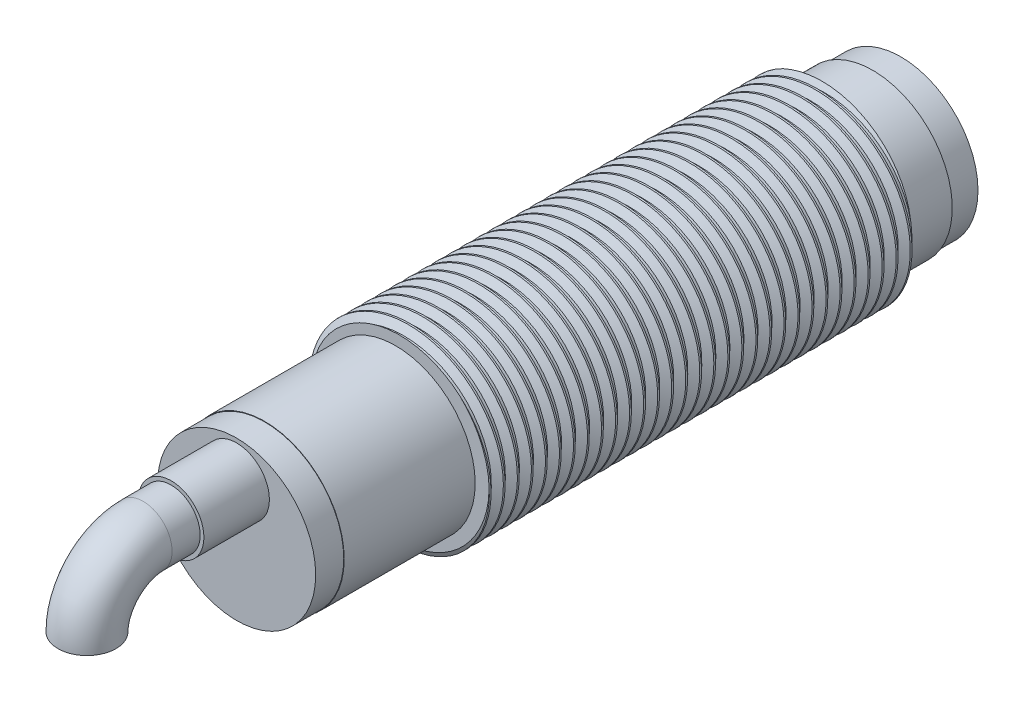
SolidWorks part; units mm, degrees
ref_plane "Front Plane" through (0, 0, 0) normal (0, 0, 1) x (1, 0, 0)
ref_plane "Top Plane" through (0, 0, 0) normal (0, 1, 0) x (1, 0, 0)
ref_plane "Right Plane" through (0, 0, 0) normal (1, 0, 0) x (0, 0, -1)
sketch "Sketch1" plane through (0, 0, 0) normal (0, 0, 1) x (1, 0, 0)
  circle A0 centre (0, 0) radius 8.25
  dimension "D1" = 16.5
extrude "Boss-Extrude1" add sketch "Sketch1" along normal blind 3
sketch "Sketch2" plane through (0, 0, 3) normal (0, 0, 1) x (1, 0, 0)
  circle A1 centre (0, 0) radius 10
  dimension "D1" = 20
extrude "Boss-Extrude2" add sketch "Sketch2" along normal blind 65
sketch "Sketch3" plane through (0, 0, 68) normal (0, 0, 1) x (1, 0, 0)
  circle A0 centre (0, 0) radius 8.45
  dimension "16.9" = 16.9
extrude "Boss-Extrude3" add sketch "Sketch3" along normal blind 3
thread "Thread1" pitch 1.5 profile "Thread Profile1" start angle 2, offset 3, length 48, pitch 1.5, diameter 20
ref_plane "Plane1" through (9.9939, 0.349, 6) normal (0.0349, -0.9994, 0) x (0.9994, 0.0349, 0)
sketch "Thread Profile1" plane through (9.9939, 0.349, 6) normal (0.0349, -0.9994, 0) x (0.9994, 0.0349, 0)
  line L0 (0, 0) -> (0, 1.5) construction
  line L11 (0, 0) -> (0, 1.3125)
  line L12 (0, 1.3125) -> (-0.8119, 0.8437)
  line L13 (-0.8119, 0.8437) -> (-0.8119, 0.4687)
  line L15 (-0.8119, 0.4687) -> (0, 0)
  line L17 (-0.8119, 0.6562) -> (0, 0.6562) construction
  point P2 (0, 0)
  dimension "Pitch" = 1.5
  dimension "Profile_Angle" = 60
  dimension "Profile_Land" = 0.375
  dimension "Profile_Height" = 0.8119
sketch "Sketch13" plane through (0, 0, 3) normal (0, 0, -1) x (-1, 0, 0)
  circle A0 centre (0, 0) radius 8.5
  circle A1 centre (0, 0) radius 12.9108
  dimension "D1" = 17
extrude "Cut-Extrude1" cut sketch "Sketch13" against normal blind 5
sketch "Sketch20" plane through (0, 0, 68) normal (0, 0, 1) x (1, 0, 0)
  circle A0 centre (0, 0) radius 8.5
  circle A1 centre (0, 0) radius 11.0505
  dimension "D1" = 17
extrude "Cut-Extrude3" cut sketch "Sketch20" against normal blind 14
sketch "Sketch21" plane through (0, 0, 71) normal (0, 0, 1) x (1, 0, 0)
  circle A0 centre (0, 4.5) radius 3.5
  dimension "D1" = 7
  dimension "D2" = 4.5
extrude "Boss-Extrude5" add sketch "Sketch21" along normal blind 7
sketch "Sketch22" plane through (0, 0, 78) normal (0, 0, 1) x (1, 0, 0)
  circle A0 centre (0, 4.5) radius 3.1
  dimension "D1" = 6.2
sketch "Sketch23" plane through (0, 0, 0) normal (1, 0, 0) x (0, 0, -1)
  line L0 (-78, 4.5) -> (-81, 4.5)
  line L1 (-78, 7.6) -> (-78, 1.4) construction
  arc A0 (-81, 4.5) -> (-87, -1.5) centre (-81, -1.5) ccw
  dimension "D1" = 6
  dimension "D2" = 3
sweep "Sweep2" add profiles "Sketch22" path "Sketch23"
